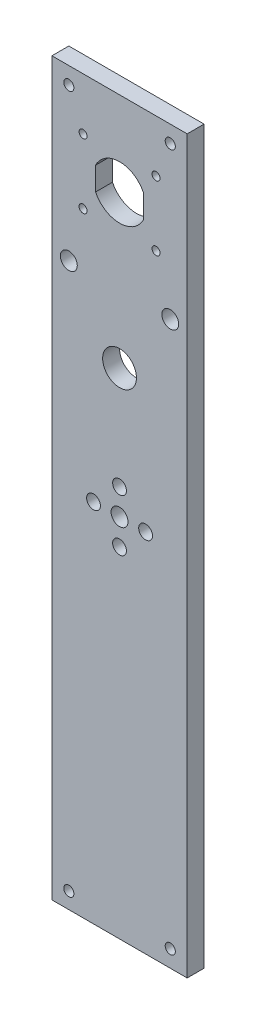
SolidWorks part; units mm, degrees
ref_plane "Front Plane" through (0, 0, 0) normal (0, 0, 1) x (1, 0, 0)
ref_plane "Top Plane" through (0, 0, 0) normal (0, 1, 0) x (1, 0, 0)
ref_plane "Right Plane" through (0, 0, 0) normal (1, 0, 0) x (0, 0, -1)
sketch "Sketch1" plane through (0, 0, 0) normal (0, 0, 1) x (1, 0, 0)
  line L1 (0, 0) -> (50.8, 0)
  line L2 (0, 0) -> (0, 274.6)
  line L3 (0, 274.6) -> (50.8, 274.6)
  line L4 (50.8, 0) -> (50.8, 274.6)
  dimension "D1" = 50.8
  dimension "D2" = 274.6
extrude "Extrude1" add sketch "Sketch1" along normal blind 6.35
hole_wizard "#10-24 Tapped Hole1" positions "3DSketch1" profile "Sketch2" tap size "#10-24" standard "Ansi Inch" end condition up to next
sketch3d "3DSketch1"
  line L0 (0, 0, 6.35) -> (50.8, 0, 6.35) construction
  line L1 (50.8, 274.6, 6.35) -> (0, 274.6, 6.35) construction
  line L2 (0, 274.6, 6.35) -> (0, 0, 6.35) construction
  point P0 (6.35, 6.096, 6.35)
  point P2 (44.4492, 6.35, 6.35)
  point P4 (44.45, 268.25, 6.35)
  point P6 (6.35, 268.25, 6.35)
  dimension "D1" = 6.096
  dimension "D2" = 6.35
  dimension "D3" = 6.35
  dimension "D4" = 6.35
  dimension "D5" = 38.1
  dimension "D6" = 38.1
  dimension "D7" = 6.35
  dimension "D8" = 6.35
sketch "Sketch2" plane through (6.35, 6.096, 6.35) normal (1, 0, 0) x (0, -1, 0)
  line L0 (0, 0) -> (0, 6.35)
  line L1 (0, 6.35) -> (1.8986, 6.35)
  line L2 (1.8986, 6.35) -> (1.8986, 0)
  line L5 (1.8986, 0) -> (0, 0)
  line L11 (0, -6.35) -> (0, 107.95) construction
  dimension "Thread Major Dia." = 3.7973
  dimension "Thru Tap Drill Depth" = 6.35
sketch "Sketch3" plane through (0, 0, 6.35) normal (0, 0, 1) x (1, 0, 0)
  line L0 (0, 0) -> (50.8, 274.6) construction
  circle A0 centre (25.4, 137.3) radius 3.175
  dimension "D1" = 6.35
extrude "Extrude2" cut sketch "Sketch3" against normal up to next
sketch "Sketch4" plane through (0, 0, 6.35) normal (0, 0, 1) x (1, 0, 0)
  line L0 (50.8, 274.6) -> (0, 274.6) construction
  line L1 (25.4, 274.6) -> (25.4, 0) construction
  line L2 (0, 0) -> (50.8, 0) construction
  line L3 (16.4, 247.2089) -> (16.4, 238.4911)
  line L4 (34.4, 247.2089) -> (34.4, 238.4911)
  line L5 (16.4, 274.6) -> (16.4, 0) construction
  line L6 (34.4, 274.6) -> (34.4, 0) construction
  arc A0 (16.4, 238.4911) -> (34.4, 238.4911) centre (25.4, 242.85) ccw
  arc A1 (34.4, 247.2089) -> (16.4, 247.2089) centre (25.4, 242.85) ccw
  dimension "D1" = 20
  dimension "D2" = 9
  dimension "D4" = 31.75
  dimension "D3" = 9
extrude "Extrude3" cut sketch "Sketch4" against normal up to next
hole_wizard "Ø3.0 (3) Diameter Hole1" positions "3DSketch4" profile "Sketch7" hole size "Ø3.0" standard "Ansi Metric" end condition up to next
sketch3d "3DSketch4"
  line L1 (11.6906, 230.7016, 6.35) -> (39.1094, 230.7016, 6.35) construction
  line L2 (11.6906, 230.7016, 6.35) -> (11.6906, 254.9984, 6.35) construction
  line L3 (11.6906, 254.9984, 6.35) -> (39.1094, 254.9984, 6.35) construction
  line L4 (39.1094, 230.7016, 6.35) -> (39.1094, 254.9984, 6.35) construction
  line L5 (11.6906, 230.7016, 6.35) -> (39.1094, 254.9984, 6.35) construction
  line L6 (11.6906, 254.9984, 6.35) -> (39.1094, 230.7016, 6.35) construction
  arc A0 (34.4, 247.2089, 6.35) -> (16.4, 247.2089, 6.35) centre (25.4, 242.85, 6.35) ccw construction
  point P0 (11.6906, 254.9984, 6.35)
  point P2 (39.1094, 254.9984, 6.35)
  point P4 (39.1094, 230.7016, 6.35)
  point P6 (11.6906, 230.7016, 6.35)
  point P9 (25.4, 242.85, 6.35)
  point P48 (25.4, 242.85, 16.35)
sketch "Sketch7" plane through (11.6906, 254.9984, 6.35) normal (1, 0, 0) x (0, -1, 0)
  line L0 (0, 0) -> (0, 6.35)
  line L1 (0, 6.35) -> (1.5, 6.35)
  line L2 (1.5, 6.35) -> (1.5, 0)
  line L5 (1.5, 0) -> (0, 0)
  line L11 (0, -6.35) -> (0, 107.95) construction
  dimension "Thru Hole Dia." = 3
  dimension "Thru Hole Depth" = 6.35
sketch "Sketch8" plane through (0, 0, 6.35) normal (0, 0, 1) x (1, 0, 0)
  line L0 (25.4, 274.6) -> (25.4, 0) construction
  line L1 (50.8, 274.6) -> (0, 274.6) construction
  line L2 (0, 0) -> (50.8, 0) construction
  circle A0 centre (25.4, 185.7) radius 6.35
  dimension "D1" = 12.7
  dimension "D2" = 88.9
extrude "Extrude4" cut sketch "Sketch8" against normal up to next
hole_wizard "#6 (0.204) Diameter Hole2" positions "3DSketch6" profile "Sketch10" hole size "#6" standard "Ansi Inch" end condition up to next
sketch3d "3DSketch6"
  line L0 (25.4, 137.3, 0) -> (25.4, 137.3, 6.35) construction
  line L1 (25.4, 127.521, 6.35) -> (25.4, 147.079, 6.35)
  line L3 (15.621, 137.3, 6.35) -> (35.179, 137.3, 6.35)
  circle A0 centre (25.4, 137.3, 6.35) radius 9.779
  point P0 (25.4, 147.079, 6.35)
  point P2 (35.179, 137.3, 6.35)
  point P4 (25.4, 127.521, 6.35)
  point P6 (15.621, 137.3, 6.35)
  point P11 (25.4, 137.3, 16.129)
  dimension "D1" = 19.558
sketch "Sketch10" plane through (25.4, 147.079, 6.35) normal (1, 0, 0) x (0, -1, 0)
  line L0 (0, 0) -> (0, 6.35)
  line L1 (0, 6.35) -> (2.5908, 6.35)
  line L2 (2.5908, 6.35) -> (2.5908, 0)
  line L5 (2.5908, 0) -> (0, 0)
  line L11 (0, -6.35) -> (0, 107.95) construction
  dimension "Thru Hole Dia." = 5.1816
  dimension "Thru Hole Depth" = 6.35
hole_wizard "1/4 (0.25) Diameter Hole1" positions "3DSketch7" profile "Sketch12" hole size "1/4" standard "Ansi Inch" end condition up to next
sketch3d "3DSketch7"
  line L0 (0, 274.6, 6.35) -> (0, 0, 6.35) construction
  line L1 (50.8, 0, 6.35) -> (50.8, 274.6, 6.35) construction
  line L2 (50.8, 274.6, 6.35) -> (0, 274.6, 6.35) construction
  point P0 (6.35, 211.1, 6.35)
  point P2 (44.45, 211.1, 6.35)
  dimension "D1" = 6.35
  dimension "D2" = 6.35
  dimension "D3" = 63.5
  dimension "D4" = 63.5
sketch "Sketch12" plane through (6.35, 211.1, 6.35) normal (1, 0, 0) x (0, -1, 0)
  line L0 (0, 0) -> (0, 6.35)
  line L1 (0, 6.35) -> (3.175, 6.35)
  line L2 (3.175, 6.35) -> (3.175, 0)
  line L5 (3.175, 0) -> (0, 0)
  line L11 (0, -6.35) -> (0, 107.95) construction
  dimension "Thru Hole Dia." = 6.35
  dimension "Thru Hole Depth" = 6.35
